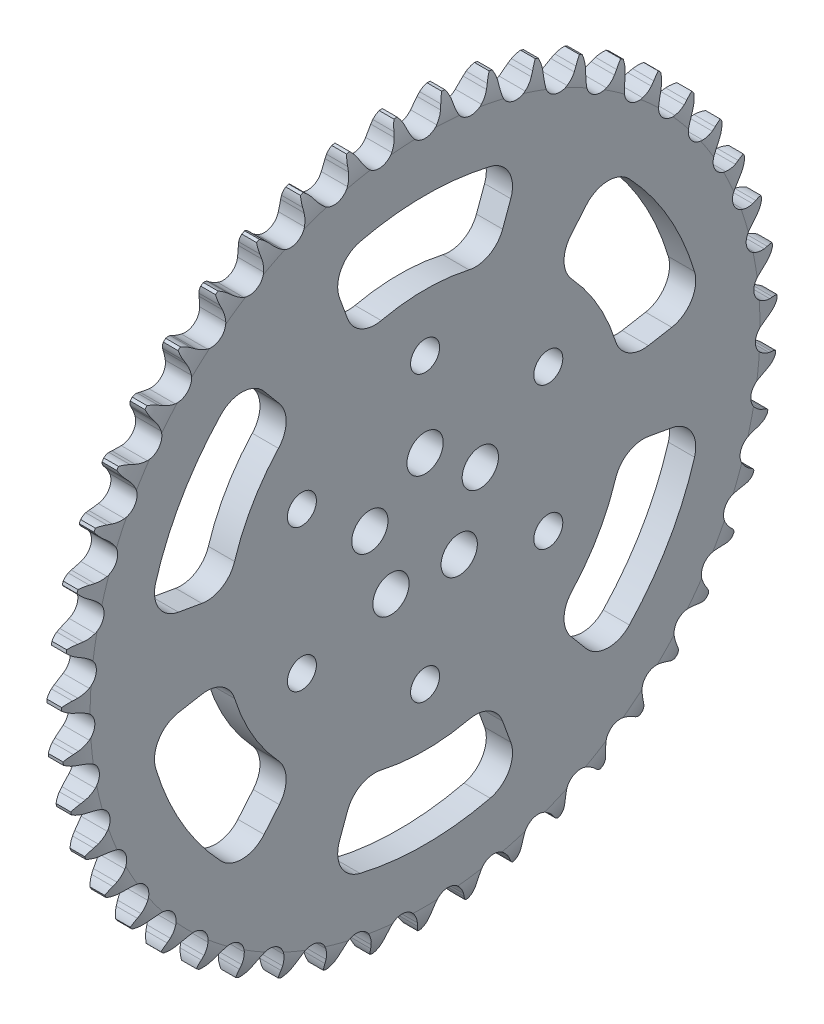
SolidWorks part; units mm, degrees
material "AISI 4340 Steel, normalized"
ref_plane "Plane1" through (0, 0, 0) normal (0, 0, 1) x (1, 0, 0)
ref_plane "Plane2" through (0, 0, 0) normal (0, 1, 0) x (1, 0, 0)
ref_plane "Plane3" through (0, 0, 0) normal (1, 0, 0) x (0, 0, -1)
sketch "Clipboard" plane through (0, 0, 0) normal (0, 1, 0) x (1, 0, 0)
  line L0 (0, 0) -> (8.6614, -9.2882)
  line L1 (-15, 0) -> (100, 0) construction
  line L2 (0, 0) -> (-1.0435, 1.1794)
  line L3 (0, 0) -> (-5.9315, 2.2671)
  line L4 (0, 0) -> (5.4047, 5.7958)
  line L5 (0, 0) -> (-47.5972, -17.7524)
  line L6 (0, 0) -> (-5.9832, -4.0369)
  line L7 (-1.0435, 1.1794) -> (32.9483, 38.9312)
  line L8 (-76.2, 38.1) -> (-61.976, 38.1)
  line L9 (-73.2057, 38.5609) -> (-73.0533, 38.5634)
  line L10 (-73.0533, 76.1892) -> (-58.6769, 76.1892)
  circle A0 centre (0, 0) radius 3.9624
  circle A1 centre (0, 0) radius 38.1
  circle A2 centre (0, 0) radius 38.1
  dimension "Dr" = 7.9248
  dimension "MHD" = 76.2
  dimension "Hub_dia" = 76.2
  dimension "Num_teeth" = 47
  dimension "Pitch" = 12.7
  dimension "Width" = 7.9248
  dimension "Chamfer_wid" = 1.5748
  dimension "Chamfer_dep" = 6.35
  dimension "Overall_len" = 50.8
  dimension "Show_teeth" = 47
  dimension "Thickness" = 7.2177
  dimension "OAL" = 50.8
  dimension "T_dim" = 14.224
  dimension "Width_const" = 0.1524
  dimension "Width_factor" = 0.93
  dimension "Num_strands" = 1
  dimension "Transv_pitch" = 14.3764
sketch "BasProSke" plane through (0, 0, 0) normal (0, 1, 0) x (1, 0, 0)
  line L0 (-10, 0) -> (60, 0) construction
  line L1 (0, 0) -> (0, 92.3181)
  line L2 (0, 0) -> (7.2177, 0)
  line L3 (7.2177, 0) -> (7.2177, 92.3181)
  line L4 (5.6429, 98.6681) -> (1.5748, 98.6681)
  arc A0 (0, 92.3181) -> (1.5748, 98.6681) centre (13.5898, 92.3181) cw
  arc A1 (7.2177, 92.3181) -> (5.6429, 98.6681) centre (-6.3722, 92.3181) ccw
  dimension "Thickness" = 7.2177
  dimension "D1" = 13.5898
  dimension "G1" = 1.5748
  dimension "G2" = 1.5748
  dimension "H2" = 6.35
  dimension "H1" = 6.35
  dimension "Diameter" = 197.3361
revolve "Base-Revolve" add sketch "BasProSke" angle 360 about L0
sketch "GrvSke" plane through (0, 0, 0) normal (0, 1, 0) x (1, 0, 0)
  line L0 (7.2177, 92.3181) -> (7.2177, 88.4931)
  line L1 (7.2177, 88.4931) -> (14.3764, 88.4931)
  line L2 (14.3764, 88.4931) -> (14.3764, 92.3181)
  line L3 (5.6429, 98.6681) -> (15.9512, 98.6681)
  line L4 (10.797, 0) -> (10.797, 52.07) construction
  line L5 (-10, 0) -> (60, 0) construction
  line L6 (0, 0) -> (35.56, 0) construction
  arc A0 (14.3764, 92.3181) -> (15.9512, 98.6681) centre (27.9662, 92.3181) cw
  arc A1 (7.2177, 92.3181) -> (5.6429, 98.6681) centre (-6.3722, 92.3181) ccw
  dimension "G1" = 1.5748
  dimension "H1" = 6.35
  dimension "Diameter" = 197.3361
  dimension "Grv_diam" = 176.9861
  dimension "Grv_width" = 7.1587
  dimension "Offset" = 10.797
revolve "Groove" [suppressed] cut sketch "GrvSke" angle 360 about L6
pattern_linear "Grooves" [suppressed]
sketch "TooCutSke" plane through (0, 0, 0) normal (1, 0, 0) x (0, 0, -1)
  line L0 (4.6223, 95.3809) -> (5.0081, 96.4721)
  line L1 (0, 0) -> (0, 107) construction
  line L2 (0, 95.0704) -> (-10, 95.0704) construction
  line L3 (-4.6223, 95.3809) -> (-5.0081, 96.4721)
  arc A0 (3.2115, 92.7133) -> (4.6223, 95.3809) centre (-5.111, 98.8215) ccw
  arc A1 (3.2115, 92.7133) -> (-3.2115, 92.7133) centre (0, 95.0704) cw
  arc A2 (5.0081, 96.4721) -> (11.0699, 100.7588) centre (11.0699, 94.3293) cw
  arc A3 (-3.2115, 92.7133) -> (-4.6223, 95.3809) centre (5.111, 98.8215) cw
  arc A4 (-5.0081, 96.4721) -> (-11.0699, 100.7588) centre (-11.0699, 94.3293) ccw
  arc A5 (11.0699, 100.7588) -> (-11.0699, 100.7588) centre (0, 0) ccw
  dimension "R" = 3.9837
  dimension "E" = 10.3236
  dimension "F" = 6.4295
  dimension "Pitch_radius" = 95.0704
  dimension "W" = 11.0699
  dimension "V" = 0.741
  dimension "A" = 36.277
  dimension "B" = 16.809
extrude "ToothCut" cut sketch "TooCutSke" along normal through all
pattern_circular "TeethCuts" count 47 every 7.66 about axis through (-10, 0, 0) along (1, 0, 0) of "ToothCut"
sketch "HubNeaOneSke" plane through (0, 0, 0) normal (-1, 0, 0) x (0, 0, 1)
  circle A0 centre (0, 0) radius 38.1
  dimension "Diameter" = 76.2
extrude "HubNearOne" [suppressed] add sketch "HubNeaOneSke" along normal blind 43.5823
sketch "HubNeaBotSke" plane through (0, 0, 0) normal (-1, 0, 0) x (0, 0, 1)
  circle A0 centre (0, 0) radius 38.1
  dimension "Diameter" = 76.2
extrude "HubNearBoth" [suppressed] add sketch "HubNeaBotSke" along normal blind 21.7912
ref_plane "FarPln" through (7.2177, 0, 0) normal (1, 0, 0) x (0, 0, -1)
sketch "HubFarSke" plane through (7.2177, 0, 0) normal (1, 0, 0) x (0, 0, -1)
  circle A0 centre (0, 0) radius 38.1
  dimension "Diameter" = 76.2
extrude "HubFar" [suppressed] add sketch "HubFarSke" along normal blind 21.7912
sketch "BorSke" plane through (0, 0, 0) normal (1, 0, 0) x (0, 0, -1)
  circle A0 centre (0, 0) radius 6.35
  dimension "Diameter" = 12.7
extrude "Bore" cut sketch "BorSke" along normal mid plane 101.6
sketch "KeySke" plane through (0, 0, 0) normal (1, 0, 0) x (0, 0, -1)
  line L0 (-1.5875, 0) -> (-1.5875, 7.874)
  line L1 (-1.5875, 7.874) -> (1.5875, 7.874)
  line L2 (1.5875, 7.874) -> (1.5875, 0)
  line L3 (0, 0) -> (0, 34) construction
  line L4 (-1.5875, 0) -> (1.5875, 0)
  dimension "Offset" = 7.874
  dimension "Width" = 3.175
extrude "Keyway" [suppressed] cut sketch "KeySke" along normal mid plane 101.6
pattern_circular "Keyway2" [suppressed] count 2 every 90 about axis through (-10, 0, 0) along (1, 0, 0) reverse direction yes
sketch "Sketch1" plane through (7.2177, 0, 0) normal (1, 0, 0) x (0, 0, -1)
  circle A6 centre (0, 0) radius 15
  dimension "D1" = 30
extrude "Boss-Extrude2" add sketch "Sketch1" against normal up to surface (7.2177 mm away) up to face at (0, 0, -6.35)
sketch "Sketch2" plane through (7.2177, 0, 0) normal (1, 0, 0) x (0, 0, -1)
  line L0 (0, 0) -> (0, 16) construction
  circle A0 centre (0, 16) radius 5
  circle A1 centre (15.2169, 4.9443) radius 5
  circle A2 centre (9.4046, -12.9443) radius 5
  circle A3 centre (-9.4046, -12.9443) radius 5
  circle A4 centre (-15.2169, 4.9443) radius 5
  point P14 (0, 0)
  dimension "D2" = 10
  dimension "D1" = 16
  dimension "D3" = 5
extrude "Cut-Extrude1" cut sketch "Sketch2" against normal through all
sketch "Sketch3" plane through (7.2177, 0, 0) normal (1, 0, 0) x (0, 0, -1)
  line L0 (0, 0) -> (0, 39.21) construction
  circle A0 centre (0, 39.21) radius 4
  circle A1 centre (33.9569, 19.605) radius 4
  circle A2 centre (33.9569, -19.605) radius 4
  circle A3 centre (0, -39.21) radius 4
  circle A4 centre (-33.9569, -19.605) radius 4
  circle A5 centre (-33.9569, 19.605) radius 4
  point P17 (0, 0)
  dimension "D1" = 8
  dimension "D2" = 39.21
  dimension "D3" = 6
extrude "Cut-Extrude2" cut sketch "Sketch3" against normal through all
sketch "Sketch4" plane through (7.2177, 0, 0) normal (1, 0, 0) x (0, 0, -1)
  line L0 (-18.8111, 51.6831) -> (-26.5066, 72.8262)
  line L1 (18.8111, 51.6831) -> (26.5066, 72.8262)
  line L2 (0, 0) -> (0, 77.5) construction
  line L3 (0, 0) -> (18.8111, 51.6831) construction
  line L4 (0, 0) -> (-18.8111, 51.6831) construction
  line L5 (0, 77.5) -> (0, 91.0867) construction
  line L6 (0, 43.21) -> (0, 55) construction
  arc A0 (26.5066, 72.8262) -> (-26.5066, 72.8262) centre (0, 0) ccw
  arc A1 (18.8111, 51.6831) -> (-18.8111, 51.6831) centre (0, 0) ccw
  arc A2 (-26.5066, 72.8262) -> (26.5066, 72.8262) centre (0, 0) ccw construction
  arc A3 (-18.8111, 51.6831) -> (18.8111, 51.6831) centre (0, 0) ccw construction
  arc A4 (-2.8377, 92.2744) -> (2.8377, 92.2744) centre (0, 95.0704) ccw construction
  circle A5 centre (0, 39.21) radius 4 construction
  dimension "D1" = 155
  dimension "D2" = 110
  dimension "D3" = 20
  dimension "D4" = 20
  dimension "D5" = 11.79
  dimension "D6" = 13.5867
extrude "Cut-Extrude3" cut sketch "Sketch4" against normal through all
fillet "Fillet1" radius 8 4 edges at (3.6088, 51.6831, -18.8111) (3.6088, 72.8262, -26.5066) (3.6088, 72.8262, 26.5066) (3.6088, 51.6831, 18.8111)
pattern_circular "CirPattern3" count 6 over 360 about axis through (0, 0, 0) along (1, 0, 0) of "Fillet1", "Cut-Extrude3"
equation "\"Num_teeth@Clipboard\" = int( \"Num_teeth@Clipboard\" )"
equation "\"Num_teeth@Clipboard\" = ((sgn( \"Num_teeth@Clipboard\" - 5.0)+1)*( \"Num_teeth@Clipboard\" - 5.0))/2 +5.0"
equation "\"Num_teeth@Clipboard\" = ((sgn( \"Num_teeth@Clipboard\" - 200.0)-1)*( \"Num_teeth@Clipboard\" - 200.0))/-2 +200.0"
equation "\"MHD@Clipboard\" = \"Pitch@Clipboard\" * (1.0 / tan(3.14159265 / \"Num_teeth@Clipboard\" ) - 1.0) - 0.03"
equation "\"Thickness@Clipboard\"  = \"Width@Clipboard\" * \"Width_factor@Clipboard\" - \"Width_const@Clipboard\" + (\"Num_strands@Clipboard\" - 1) * \"Transv_pitch@Clipboard\""
equation "\"OAL@Clipboard\" = \"Thickness@Clipboard\""
equation "\"MHD@Clipboard\" = ((sgn( \"MHD@Clipboard\" - \"Hub_dia@Clipboard\" )-1)*( \"MHD@Clipboard\" - \"Hub_dia@Clipboard\" ))/-2+ \"Hub_dia@Clipboard\""
equation "\"OAL@Clipboard\" = ((sgn( \"OAL@Clipboard\" - \"Overall_len@Clipboard\" )+1)*( \"OAL@Clipboard\" - \"Overall_len@Clipboard\" ))/2 + \"Overall_len@Clipboard\" + 0.000002"
equation "\"Num_teeth@TeethCuts\" = int( \"Show_teeth@Clipboard\" ) + 1"
equation "\"Num_teeth@TeethCuts\" = ((sgn( \"Num_teeth@TeethCuts\" - \"Num_teeth@Clipboard\" )-1)*( \"Num_teeth@TeethCuts\" - \"Num_teeth@Clipboard\" ))/-2+ \"Num_teeth@Clipboard\""
equation "\"Num_teeth@TeethCuts\" = ((sgn( \"Num_teeth@TeethCuts\" - 2.0)+1)*( \"Num_teeth@TeethCuts\" - 2.0))/2 +2.0"
equation "\"Angle@TeethCuts\" = 360.0 / \"Num_teeth@Clipboard\""
equation "\"Pitch_radius@TooCutSke\" = ( \"Pitch@Clipboard\" / 2.0) / sin(3.14159265 / \"Num_teeth@Clipboard\" )  'ma"
equation "\"R@TooCutSke\"  = \"Dr@Clipboard\" * 0.5025 + 0.0015"
equation "\"A@TooCutSke\" = 35.0 + (60.0 / \"Num_teeth@Clipboard\")"
equation "\"E@TooCutSke\"  = \"Dr@Clipboard\" * 1.3025 + 0.0015"
equation "\"B@TooCutSke\"  = 18.0 - (56.0 / \"Num_teeth@Clipboard\" )"
equation "\"W@TooCutSke\" = 1.4 * \"Dr@Clipboard\" * cos(3.14159265 / \"Num_teeth@Clipboard\" )"
equation "\"V@TooCutSke\" = 1.4 * \"Dr@Clipboard\" * sin(3.14159265 / \"Num_teeth@Clipboard\" )"
equation "\"Diameter@BasProSke\" = 2.0 * ( (0.3 * \"Pitch@Clipboard\" ) +  \"Pitch@Clipboard\" / 2.0 / tan(3.14159265 / \"Num_teeth@Clipboard\" ))"
equation "\"Thickness@BasProSke\"  = \"Thickness@Clipboard\""
equation "\"G1@BasProSke\" =  \"Chamfer_wid@Clipboard\""
equation "\"G2@BasProSke\" =  \"Chamfer_wid@Clipboard\""
equation "\"H1@BasProSke\" =  \"Chamfer_dep@Clipboard\""
equation "\"H2@BasProSke\" =  \"Chamfer_dep@Clipboard\""
equation "\"Diameter@GrvSke\" = \"Diameter@BasProSke\""
equation "\"G1@GrvSke\" = \"Chamfer_wid@Clipboard\""
equation "\"H1@GrvSke\" = \"Chamfer_dep@Clipboard\""
equation "\"Grv_diam@GrvSke\" =  \"Pitch@Clipboard\" * (1.0 / tan(3.14159265 / \"Num_teeth@Clipboard\" ) - 1.0) - 0.03"
equation "\"Grv_width@GrvSke\" =  \"Transv_pitch@Clipboard\" - ( \"Width@Clipboard\" * \"Width_factor@Clipboard\" - \"Width_const@Clipboard\" )"
equation "\"Offset@GrvSke\" = \"Grv_width@GrvSke\" / 2.0 + ( \"Width@Clipboard\" * \"Width_factor@Clipboard\" - \"Width_const@Clipboard\" )"
equation "\"Offset@Grooves\" = \"Transv_pitch@Clipboard\""
equation "\"Num_grvs@Grooves\" = \"Num_strands@Clipboard\""
equation "\"Num_grvs@Grooves\" = \"Num_grvs@Grooves\" - 1 * sgn( \"Num_grvs@Grooves\" -1)"
equation "\"Diameter@HubNeaOneSke\" = \"MHD@Clipboard\""
equation "\"Length@HubNearOne\" = \"OAL@Clipboard\" - \"Thickness@BasProSke\""
equation "\"Diameter@HubNeaBotSke\" = \"MHD@Clipboard\""
equation "\"Length@HubNearBoth\" = ( \"OAL@Clipboard\" - \"Thickness@BasProSke\" ) / 2.0"
equation "\"Thickness@FarPln\" = \"Thickness@BasProSke\""
equation "\"Diameter@HubFarSke\" = \"MHD@Clipboard\""
equation "\"Length@HubFar\" = ( \"OAL@Clipboard\" - \"Thickness@BasProSke\" ) / 2.0"
equation "\"D1@Bore\" = \"OAL@Clipboard\" * 2.0"
equation "\"D1@Keyway\" = \"OAL@Clipboard\" * 2.0"
equation "\"Offset@KeySke\" = \"T_dim@Clipboard\" - \"Diameter@BorSke\" / 2.0"
equation "\"D4@Sketch4\"=\"D3@Sketch4\""
